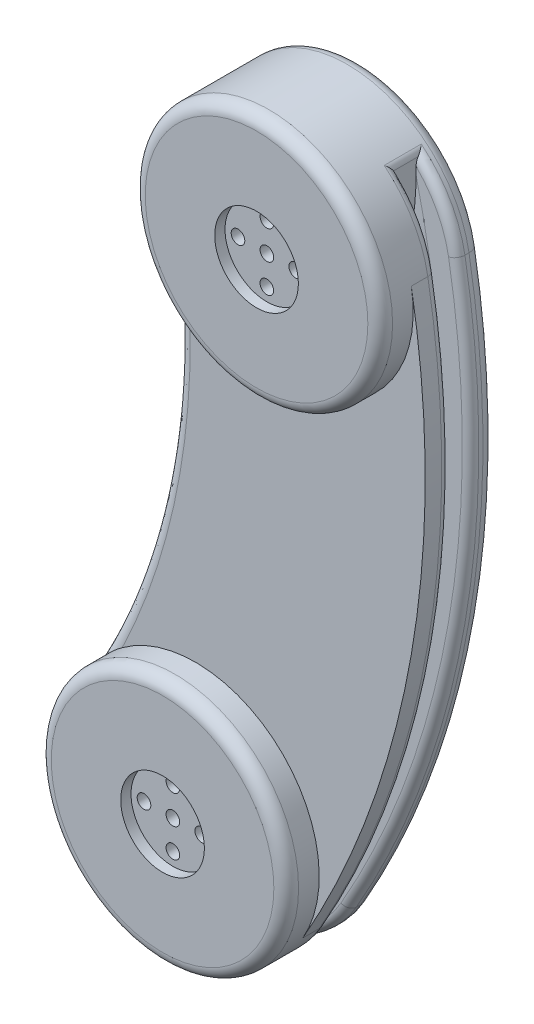
SolidWorks part; units mm, degrees
ref_plane "Front Plane" through (0, 0, 0) normal (0, 0, 1) x (1, 0, 0)
ref_plane "Top Plane" through (0, 0, 0) normal (0, 1, 0) x (1, 0, 0)
ref_plane "Right Plane" through (0, 0, 0) normal (1, 0, 0) x (0, 0, -1)
sketch "Sketch1" plane through (0, 0, 0) normal (0, 0, 1) x (1, 0, 0)
  line L0 (0, 66.9994) -> (0, 0) construction
  arc A2 (0, 66.9994) -> (-22.8, -63.0006) centre (-191.007, 33.4997) cw construction
  arc A3 (3.2218, -77.9293) -> (29.549, 72.1818) centre (-191.007, 33.4997) ccw
  arc A4 (-48.8218, -48.0719) -> (-29.549, 61.8169) centre (-191.007, 33.4997) ccw
  arc A5 (-48.8218, -48.0719) -> (3.2218, -77.9293) centre (-22.8, -63.0006) ccw
  arc A6 (29.549, 72.1818) -> (-29.549, 61.8169) centre (0, 66.9994) ccw
  point P3 (0, 0)
  dimension "D1" = 30
  dimension "D2" = 130
  dimension "D3" = 22.8
extrude "Boss-Extrude1" add sketch "Sketch1" along normal mid plane 25
sketch "Sketch2" plane through (0, 0, 12.5) normal (0, 0, 1) x (1, 0, 0)
  arc A0 (-29.549, 61.8169) -> (29.549, 72.1818) centre (0, 66.9994) ccw
  arc A1 (3.2218, -77.9293) -> (-48.8218, -48.0719) centre (-22.8, -63.0006) ccw
  arc A2 (-48.8218, -48.0719) -> (3.2218, -77.9293) centre (-22.8, -63.0006) ccw construction
  arc A7 (-48.8218, -48.0719) -> (3.2218, -77.9293) centre (-22.8, -63.0006) ccw
  arc A8 (3.2218, -77.9293) -> (29.549, 72.1818) centre (-191.007, 33.4997) ccw
  arc A9 (29.549, 72.1818) -> (-29.549, 61.8169) centre (0, 66.9994) ccw
  arc A10 (-48.8218, -48.0719) -> (-29.549, 61.8169) centre (-191.007, 33.4997) ccw
  arc A12 (3.2218, -77.9293) -> (29.549, 72.1818) centre (-191.007, 33.4997) ccw
  arc A14 (-48.8218, -48.0719) -> (-29.549, 61.8169) centre (-191.007, 33.4997) ccw
  dimension "D1" = 0
extrude "Cut-Extrude1" cut sketch "Sketch2" against normal blind 8
sketch "Sketch3" plane through (0, 0, -12.5) normal (0, 0, -1) x (-1, 0, 0)
  arc A4 (-3.2218, -77.9293) -> (48.8218, -48.0719) centre (22.8, -63.0006) ccw
  arc A5 (29.549, 61.8169) -> (48.8218, -48.0719) centre (191.007, 33.4997) ccw
  arc A6 (29.549, 61.8169) -> (-29.549, 72.1818) centre (0, 66.9994) ccw
  arc A7 (-29.549, 72.1818) -> (-3.2218, -77.9293) centre (191.007, 33.4997) ccw
  arc A8 (-3.2218, -77.9293) -> (48.8218, -48.0719) centre (22.8, -63.0006) ccw
  arc A9 (29.549, 61.8169) -> (48.8218, -48.0719) centre (191.007, 33.4997) ccw
  arc A10 (29.549, 61.8169) -> (-29.549, 72.1818) centre (0, 66.9994) ccw
  arc A11 (-29.549, 72.1818) -> (-3.2218, -77.9293) centre (191.007, 33.4997) ccw
  dimension "D1" = 0
extrude "Boss-Extrude2" add sketch "Sketch3" against normal blind 4
ref_plane "Plane1" through (0, 0, -4) normal (0, 0, 1) x (1, 0, 0)
sketch "Sketch7" plane through (0, 0, -4) normal (0, 0, 1) x (1, 0, 0)
  line L2 (19.6993, 70.4543) -> (19.6993, 92.1818)
  line L3 (19.6993, 92.1818) -> (29.549, 92.1818)
  line L4 (29.549, 92.1818) -> (29.549, 72.1818)
  line L5 (-5.4521, -72.9531) -> (-5.4521, -97.9293)
  line L6 (-5.4521, -97.9293) -> (3.2218, -97.9293)
  line L7 (3.2218, -97.9293) -> (3.2218, -77.9293)
  arc A0 (29.549, 72.1818) -> (3.2218, -77.9293) centre (-191.007, 33.4997) cw
  arc A1 (19.6993, 70.4543) -> (-5.4521, -72.9531) centre (-191.007, 33.4997) cw
  dimension "D1" = 223.9224
  dimension "D3" = 20
  dimension "D4" = 20
  dimension "D2" = 10
extrude "Cut-Extrude5" cut sketch "Sketch7" against normal mid plane 5
fillet "Fillet1" radius 3 8 edges at (-37.7287, -89.0224, -12.5) (-5.1824, 96.5484, -12.5) (-29.549, 5.1824, -12.5) (29.549, -5.1824, -12.5) (-29.549, 5.1824, 4.5) (19.6993, -3.455, -6.5) (7.2, -63.0006, 12.5) (30, 66.9994, 12.5)
fillet "Fillet2" radius 2 8 edges at (26.1231, 81.75, -6.5) (29.549, -5.1824, -6.5) (26.1231, 81.75, -1.5) (29.549, -5.1824, -1.5) (19.6993, 89.6254, -4) (-0.596, -83.1744, -6.5) (-0.596, -83.1744, -1.5) (-5.4521, -87.4761, -4)
sketch "Sketch9" plane through (0, 0, -12.5) normal (0, 0, -1) x (-1, 0, 0)
  arc A0 (26.5941, 62.3352) -> (46.2196, -49.5648) centre (191.007, 33.4997) ccw construction
  arc A1 (26.5941, 62.3352) -> (46.2196, -49.5648) centre (191.007, 33.4997) ccw construction
sketch "Sketch10" plane through (0, 0, -12.5) normal (0, 0, -1) x (-1, 0, 0)
  text T0 "\r\nF   O   R   G   E" font "Impact" height in points 72
extrude "Cut-Extrude6" cut sketch "Sketch10" against normal blind 1
sketch "Sketch11" plane through (0, 0, -4) normal (0, 0, 1) x (1, 0, 0)
  line L0 (-27.4807, 0) -> (0, 0) construction
  arc A0 (-46.2196, -49.5648) -> (-26.5941, 62.3352) centre (-191.007, 33.4997) ccw construction
sketch "Sketch13" plane through (0, 0, 12.5) normal (0, 0, 1) x (1, 0, 0)
  circle A0 centre (-22.8, -63.0006) radius 10.15
  circle A1 centre (0, 66.9994) radius 10.15
  dimension "D1" = 20.3
extrude "Cut-Extrude7" cut sketch "Sketch13" against normal blind 2.5
sketch "Sketch14" plane through (0, 0, 10) normal (0, 0, 1) x (1, 0, 0)
  circle A0 centre (-22.8, -63.0006) radius 1.65
  circle A1 centre (0, 66.9994) radius 1.65
  circle A2 centre (0, 73.9994) radius 1.65
  circle A3 centre (7, 66.9994) radius 1.65
  circle A4 centre (0, 59.9994) radius 1.65
  circle A5 centre (-7, 66.9994) radius 1.65
  circle A6 centre (-22.8, -56.0006) radius 1.65
  circle A7 centre (-15.8, -63.0006) radius 1.65
  circle A8 centre (-22.8, -70.0006) radius 1.65
  circle A9 centre (-29.8, -63.0006) radius 1.65
  dimension "D1" = 3.3
  dimension "D2" = 3.3
  dimension "D5" = 3.3
  dimension "D3" = 7
  dimension "D6" = 7
  dimension "D4" = 4
  dimension "D7" = 4
extrude "Cut-Extrude8" cut sketch "Sketch14" against normal through all and the other way through all
